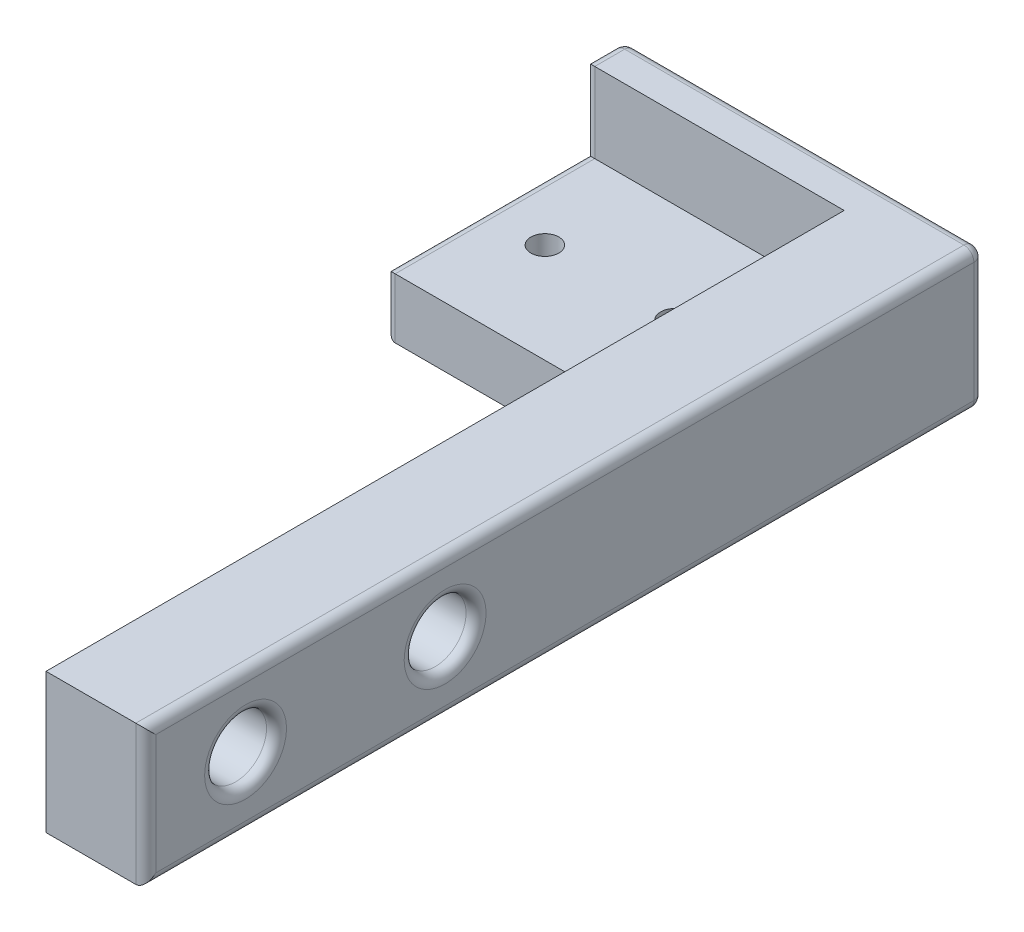
SolidWorks part; units mm, degrees
ref_plane "前视基准面" through (0, 0, 0) normal (0, 0, 1) x (1, 0, 0)
ref_plane "上视基准面" through (0, 0, 0) normal (0, 1, 0) x (1, 0, 0)
ref_plane "右视基准面" through (0, 0, 0) normal (1, 0, 0) x (0, 0, -1)
sketch "草图1" plane through (0, 0, 0) normal (0, 1, 0) x (1, 0, 0)
  line L0 (-12.5, 15) -> (-12.5, 20) construction
  line L2 (-2.5, 15) -> (-2.5, -15)
  line L3 (-2.5, -15) -> (2.5, -15)
  line L4 (2.5, 15) -> (2.5, -15)
  line L5 (-2.5, 15) -> (2.5, -15) construction
  line L6 (-2.5, -15) -> (2.5, 15) construction
  line L7 (-2.5, 15) -> (-15.5, 15)
  line L8 (2.5, 15) -> (2.5, 25)
  line L9 (2.5, 25) -> (-15.5, 25)
  line L10 (-15.5, 15) -> (-15.5, 25)
  line L11 (-12.5, 20) -> (-15.5, 20) construction
  line L12 (-12.5, 20) -> (-6, 20) construction
  circle A0 centre (-12.5, 20) radius 0.7
  circle A1 centre (-6, 20) radius 0.7
  point P0 (0, 0)
  dimension "D8" = 1.4
  dimension "D9" = 1.4
  dimension "D1" = 10
  dimension "D2" = 30
  dimension "D3" = 18
  dimension "D4" = 5
  dimension "D5" = 3
  dimension "D6" = 5
  dimension "D7" = 6.5
extrude "凸台-拉伸1" add sketch "草图1" along normal blind 7
sketch "草图2" plane through (2.5, 0, 0) normal (1, 0, 0) x (0, 0, -1)
  line L0 (-15, 3.5) -> (-10, 3.5) construction
  line L1 (-15, 7) -> (-15, 0) construction
  line L2 (-10, 3.5) -> (0, 3.5) construction
  circle A0 centre (-10, 3.5) radius 1.55
  circle A1 centre (0, 3.5) radius 1.55
  dimension "D3" = 3.1
  dimension "D4" = 3.1
  dimension "D1" = 5
  dimension "D2" = 10
extrude "切除-拉伸1" cut sketch "草图2" against normal through all
sketch "草图3" plane through (0, 7, 0) normal (0, 1, 0) x (1, 0, 0)
  line L1 (-15.5, 15) -> (-2.5, 15)
  line L2 (-15.5, 15) -> (-15.5, 25)
  line L3 (-15.5, 25) -> (-2.5, 25)
  line L4 (-2.5, 15) -> (-2.5, 25)
  dimension "D1" = 13
  dimension "D2" = 10
extrude "切除-拉伸2" cut sketch "草图3" against normal blind 4
sketch "草图4" plane through (0, 0, 0) normal (0, -1, 0) x (1, 0, 0)
  line L1 (-15.5, -25) -> (2.5, -25)
  line L2 (-15.5, -25) -> (-15.5, -27)
  line L3 (-15.5, -27) -> (2.5, -27)
  line L4 (2.5, -25) -> (2.5, -27)
  dimension "D1" = 2
extrude "凸台-拉伸2" add sketch "草图4" against normal blind 7
fillet "圆角1" radius 0.5 9 edges at (2.5, 3.5, 15) (2.5, 7, -6) (2.5, 0, -6) (2.5, 3.5, -1.55) (2.5, 3.5, 8.45) (2.5, 3.5, -27) (-6.5, 7, -27) (-15.5, 3.5, -27) (-6.5, 0, -27)
fillet "圆角2" radius 0.5 7 edges at (-15.3536, 0.1464, -26.8536) (-15.3536, 6.8536, -26.8536) (-15.5, 5, -25) (-15.5, 3, -20) (-15.5, 1.5, -15) (-15.5, 0, -20.75) (-15.5, 7, -25.75)
